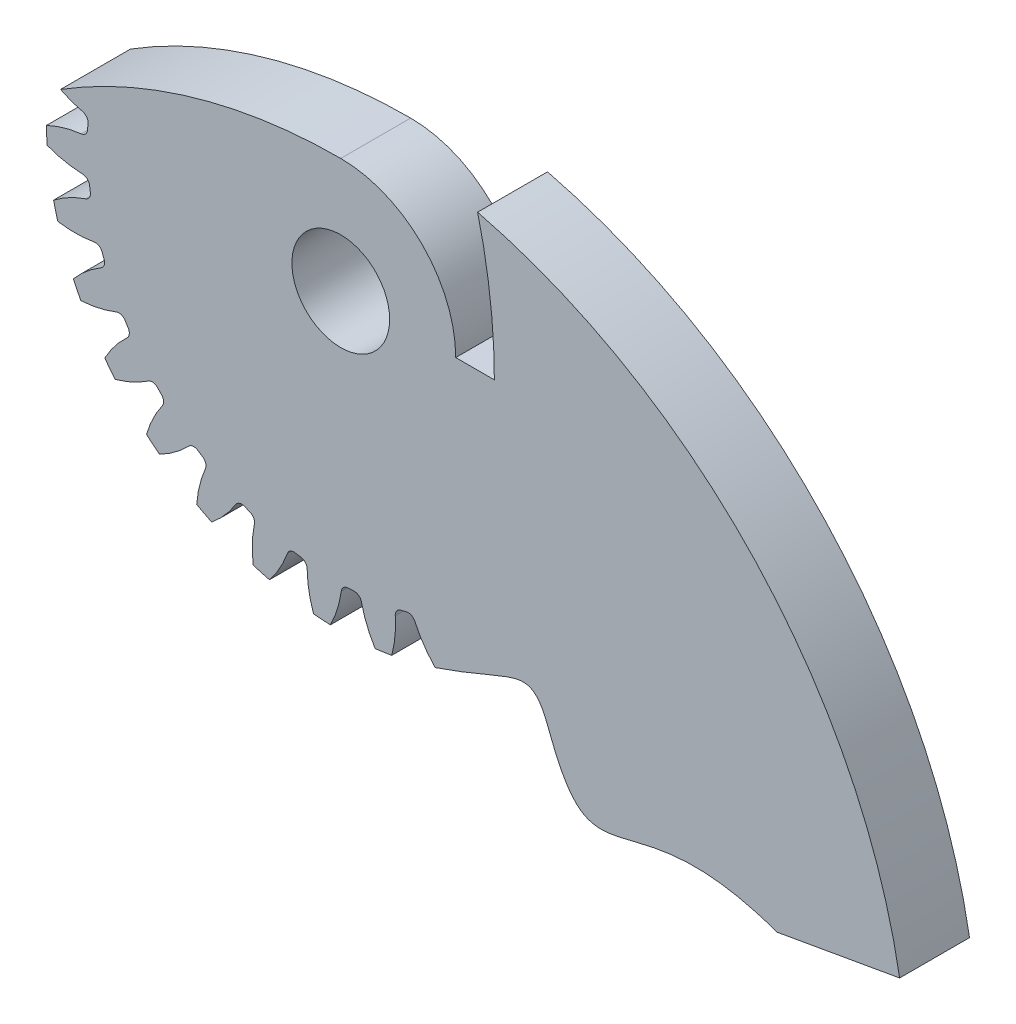
SolidWorks part; units mm, degrees
material "ABS"
ref_plane "Front" through (0, 0, 0) normal (0, 0, 1) x (1, 0, 0)
ref_plane "Top" through (0, 0, 0) normal (0, 1, 0) x (1, 0, 0)
ref_plane "Right" through (0, 0, 0) normal (1, 0, 0) x (0, 0, -1)
sketch "Sketch3" plane through (0, 0, 0) normal (0, 0, 1) x (1, 0, 0)
  circle A0 centre (0, 0) radius 40.64
  dimension "od" = 81.28
extrude "gearBody" add sketch "Sketch3" along normal blind 9.652
sketch "Sketch2" plane through (0, 0, 0) normal (0, 0, 1) x (1, 0, 0)
  line L0 (0, 0) -> (34.0786, 14.1158) construction
  line L1 (45.4751, -11.4855) -> (0, 0) construction
  line L2 (0, 0) -> (36.3143, 0) construction
  line L3 (38.0972, -0.458) -> (37.8451, -4.4001) construction
  line L5 (37.9712, -2.4291) -> (0, 0) construction
  line L7 (0, 0) -> (36.8864, 0) construction
  arc A0 (36.879, -0.7403) -> (36.6727, -3.9649) centre (0, 0) ccw construction
  arc A1 (40.637, 0.4947) -> (40.2427, -5.6687) centre (0, 0) ccw construction
  arc A2 (38.0972, -0.458) -> (37.8451, -4.4001) centre (0, 0) ccw construction
  arc A3 (34.9015, -2.6404) -> (34.9534, -1.8283) centre (0, 0) ccw
  arc A4 (45.4751, -11.4855) -> (35.6466, -3.6712) centre (32.0022, -18.3431) ccw
  arc A5 (45.4751, -11.4855) -> (46.5679, 5.5974) centre (0, 0) ccw
  arc A6 (46.5679, 5.5974) -> (35.8238, -0.9008) centre (34.0786, 14.1158) cw
  arc A7 (34.9534, -1.8283) -> (35.8238, -0.9008) centre (35.9376, -1.8798) cw
  arc A8 (35.6466, -3.6712) -> (34.9015, -2.6404) centre (35.8842, -2.7147) cw
  point P6 (46.5679, 5.5974)
  point P22 (45.4751, -11.4855)
  dimension "baseDia" = 73.7729
  dimension "od" = 81.28
  dimension "pd" = 76.2
  dimension "rd" = 70.0024
  dimension "rFillet" = 0.9855
  dimension "pointX" = 46.5679
  dimension "pointY" = 5.5974
  dimension "CTT" = 3.9421
  dimension "flankCenterAngle" = 22.5
extrude "toothCut" cut sketch "Sketch2" along normal through all
pattern_circular "CirPattern1" count 30 over 360 about axis through (0, 0, 9.652) along (0, 0, -1) of "toothCut"
sketch "hub1Dia" plane through (0, 0, 0) normal (0, 0, -1) x (-1, 0, 0)
  circle A0 centre (0, 0) radius 12.7
  dimension "hub1Dia" = 25.4
sketch "hub2Dia" plane through (0, 0, 9.652) normal (0, 0, 1) x (1, 0, 0)
  circle A0 centre (0, 0) radius 12.7
  dimension "hub2dia" = 25.4
sketch "boreDia" plane through (0, 0, 0) normal (0, 0, 1) x (1, 0, 0)
  circle A0 centre (0, 0) radius 6.7469
  dimension "boreDia" = 13.4937
extrude "bore" cut sketch "boreDia" against normal mid plane 25400
sketch "Sketch4" plane through (0, 0, 9.652) normal (0, 0, 1) x (1, 0, 0)
  circle A0 centre (0, -57.15) radius 78.359
  arc A2 (-42.9159, 8.4119) -> (42.9159, 8.4119) centre (0, 0) cw
  dimension "D1" = 156.718
  dimension "D2" = 57.15
extrude "Cut-Extrude1" cut sketch "Sketch4" against normal through all contours A0 region at (0, 27.8712, 9.652)
sketch "Sketch5" plane through (0, 0, 9.652) normal (0, 0, 1) x (1, 0, 0)
  line L0 (0, 21.209) -> (21.5163, 5.902)
  line L1 (21.5163, 5.902) -> (8.9608, -26.928)
  line L2 (8.9608, -26.928) -> (13.028, -38.4952)
  line L3 (0, 0) -> (0, -57.15) construction
  line L4 (0, -57.15) -> (-55.7146, -2.05) construction
  line L5 (0, -57.15) -> (67.8609, -96.3295) construction
  line L9 (0, -57.15) -> (77.1686, -43.5431) construction
  line L12 (60.232, -46.5295) -> (77.1686, -43.5431)
  line L13 (0, -57.15) -> (29.696, -40.005) construction
  line L14 (29.696, -40.005) -> (26.521, -34.5057) construction
  circle A1 centre (0, -57.15) radius 78.359 construction
  arc A5 (0, 21.209) -> (77.1686, -43.5431) centre (0, -57.15) cw
  circle A6 centre (0, -57.15) radius 21.59 construction
  circle A12 centre (49.4934, -85.725) radius 40.64 construction
  spline S0 degree 3 poles (13.028, -38.4952) (20.557, -35.948) (26.6517, -31.726) (34.6651, -56.7545) (39.5345, -39.0169) (60.232, -46.5295) knots 0 0 0 0 0.118515 0.218515 1 1 1 1
  point P28 (21.569, -56.1981)
  dimension "D1" = 43.18
  dimension "D3" = 81.28
  dimension "D6" = 156.718
  dimension "D2" = 120
  dimension "D4" = 57.15
  dimension "D8" = 57.15
  dimension "D7" = 60
  dimension "D9" = 34.29
  dimension "D10" = 6.35
  dimension "D5" = 80
extrude "Boss-Extrude1" add sketch "Sketch5" against normal up to surface (9.652 mm away) up to face at (6.7469, 0, 0)
sketch "Sketch6" plane through (0, 0, 9.652) normal (0, 0, 1) x (1, 0, 0)
  line L1 (-41.2993, 3.0747) -> (-43.5539, 7.9898)
  line L2 (15.875, 0) -> (21.209, 0)
  circle A0 centre (0, -57.15) radius 78.359 construction
  arc A1 (77.1686, -43.5431) -> (-36.286, 12.3011) centre (0, -57.15) ccw construction
  circle A2 centre (0, 0) radius 15.875 construction
  arc A3 (0, 15.875) -> (15.875, 0) centre (0, 0) cw
  arc A4 (18.8964, 18.8964) -> (-43.5539, 7.9898) centre (0, -57.15) ccw
  arc A5 (0, 15.875) -> (-41.2993, 3.0747) centre (0, -57.15) ccw
  circle A6 centre (0, 0) radius 21.209 construction
  circle A8 centre (-57.15, 0) radius 78.359 construction
  arc A9 (21.209, 0) -> (18.8964, 18.8964) centre (-57.15, 0) ccw
  dimension "D4" = 57.15
  dimension "D1" = 31.75
  dimension "D2" = 42.418
  dimension "D3" = 156.718
extrude "Cut-Extrude2" cut sketch "Sketch6" against normal through all
equation "\"Bodytube_OD\" = 6.17in"
equation "\"Bodytube_ID\" = 5.998in"
equation "\"Fwd_Tube_Length\" = 40in"
equation "\"Mid_Tube_Length\" = 1in"
equation "\"Aft_Section_Length\"= 39in"
equation "\"Mid_Coupler_Length\"= 13in"
equation "\"Aft_Lower_Length\"= 22in"
equation "\"AB_Coupler_OD_Length\"= 1in"
equation "\"AB_Coupling_Section_Length\"= 0.375in"
equation "\"AB_Coupler_Length\"= \"AB_Coupler_OD_Length\" + \"AB_Coupling_Section_Length\" * 2"
equation "\"Cutout_Angle\" = 80"
equation "\"AB_Paddle_Height\" = 0.375in"
equation "\"AB_Coupler_Num_Screws\"= 6"
equation "\"Num_Cutouts\" = 3"
equation "\"AB_Coupler_OD\"= 6.17in"
equation "\"AB_Coupler_ID\"= 5.75in"
equation "\"AB_Coupler_Surface_Diameter\"= 5.998in"
equation "\"AB_Coupling_Screw_Diameter\"= 0.1065in"
equation "\"AB_Central_Bushing_Length\" = .75in"
equation "\"Lead_Screw_Dist\" = 2.25in"
equation "\"Lead_Screw_Diam\" = 11mm"
equation "\"Lead_Screw_Length\" = (\"Mid_Coupler_Length\" + 2*0.375in + 2*0.5in)"
equation "\"Paddle_Pin_Offset\" = .25in"
equation "\"Paddle_Pin_Radius\" = 2.25in"
equation "\"Fwd_BKHD_From_Top\" = 18in"
equation "\"D1@Sketch4\"=\"Bodytube_OD\""
equation "\"D2@Sketch4\"=\"Paddle_Pin_Radius\""
equation "\"D3@Sketch5\"=\"Paddle_Gear_OD\""
equation "\"D4@Sketch5\"=\"Paddle_Pin_Radius\""
equation "\"Motor_OD\" = 4in"
equation "\"Aft_Upper_Length\"= \"Aft_Section_Length\" - \"Aft_Lower_Length\" - \"AB_Coupler_OD_Length\""
equation "\"Paddle_Gear_OD\" = 3.2in"
equation "\"D5@Sketch5\"=\"Cutout_Angle\""
equation "\"D6@Sketch5\"=\"Bodytube_OD\""
equation "\"D1@Sketch6\"=\"AB_Coupler_ID\"-2*\"Paddle_Pin_Radius\""
equation "\"D2@Sketch6\"=\"Bodytube_OD\"-2*\"Paddle_Pin_Radius\""
equation "\"D3@Sketch6\"=\"Bodytube_OD\""
equation "\"D4@Sketch6\"=\"Paddle_Pin_Radius\""
equation "\"D8@Sketch5\"=\"Paddle_Pin_Radius\""
equation "\"Drive_Gear_OD\" = 1.7in"
equation "\"Fin_Thickness\"= .118in"
equation "\"Guiderail_Cutout_Diameter\"= 1.5in"
equation "\"DB9_Hole_Dist\" = 25mm"
equation "\"D1@Sketch5\"=\"Drive_Gear_OD\""
